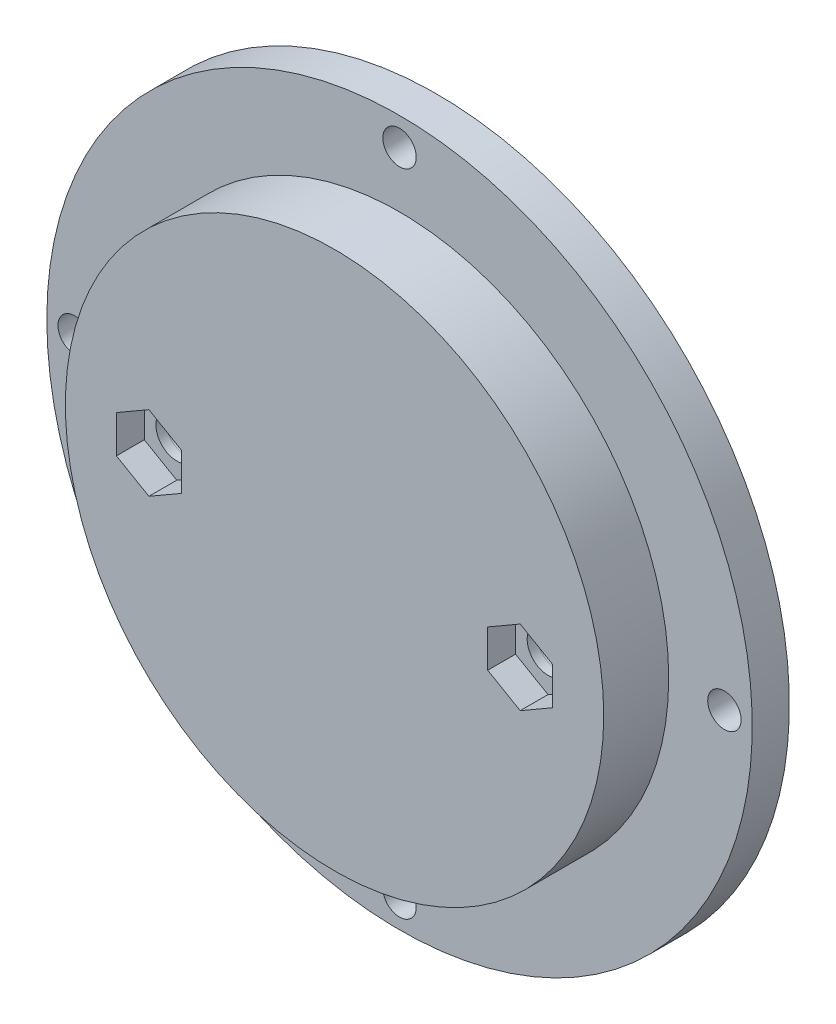
SolidWorks part; units mm, degrees
material "ｽﾃﾝﾚｽ鋼(鋳造)"
ref_plane "正面" through (0, 0, 0) normal (0, 0, 1) x (1, 0, 0)
ref_plane "平面" through (0, 0, 0) normal (0, 1, 0) x (1, 0, 0)
ref_plane "右側面" through (0, 0, 0) normal (1, 0, 0) x (0, 0, -1)
sketch "ｽｹｯﾁ1" plane through (0, 0, 0) normal (0, 1, 0) x (1, 0, 0)
  line L0 (0, 1.7) -> (0, 19.9)
  line L1 (0, 1.7) -> (0, 0) construction
  arc A0 (0, 19.9) -> (0, 1.7) centre (0, 10.8) cw
  dimension "D1" = 9.1
  dimension "D2" = 19.9
revolve "回転1" add sketch "ｽｹｯﾁ1" angle 360 about L0
sketch "ｽｹｯﾁ2" plane through (0, 0, 0) normal (0, 0, 1) x (1, 0, 0)
  line L0 (20, 0) -> (-20, 0) construction
  line L1 (-26, 0) -> (-20, 0) construction
  line L2 (-24.0086, 1.5704) -> (-9.9696, 12.6419)
  line L3 (-24.0086, -1.5704) -> (-9.9696, -12.6419)
  line L4 (0, -5.005) -> (0, 5.005) construction
  line L5 (24.0086, -1.5704) -> (9.9696, -12.6419)
  line L6 (24.0086, 1.5704) -> (9.9696, 12.6419)
  circle A0 centre (-20, 0) radius 2.25
  circle A1 centre (20, 0) radius 2.25
  arc A2 (-9.9696, -12.6419) -> (9.9696, -12.6419) centre (0, 0) ccw
  arc A3 (9.9696, 12.6419) -> (-9.9696, 12.6419) centre (0, 0) ccw
  arc A4 (24.0086, -1.5704) -> (24.0086, 1.5704) centre (22.7702, 0) ccw
  arc A5 (-24.0086, 1.5704) -> (-24.0086, -1.5704) centre (-22.7702, 0) ccw
  point P4 (0, 0)
  point P21 (26, 0)
  dimension "D2" = 4.5
  dimension "D3" = 32.2
  dimension "D4" = 2
  dimension "D1" = 40
  dimension "D5" = 26
extrude "ﾎﾞｽ - 押し出し1" add sketch "ｽｹｯﾁ2" against normal blind 1 separate body
sketch "ｽｹｯﾁ3" plane through (0, 0, -1) normal (0, 0, -1) x (-1, 0, 0)
  circle A0 centre (0, 0) radius 14.1
  arc A1 (-9.9696, -12.6419) -> (9.9696, -12.6419) centre (0, 0) ccw construction
  dimension "D1" = 2
extrude "ﾎﾞｽ - 押し出し2" add sketch "ｽｹｯﾁ3" along normal blind 14.35
fillet "ﾌｨﾚｯﾄ1" radius 4 1 edges at (-14.1, 0, -15.35)
fillet "ﾌｨﾚｯﾄ2" radius 2 1 edges at (-14.1, 0, -1)
sketch "ｽｹｯﾁ4" plane through (0, 0, 0) normal (1, 0, 0) x (0, 0, -1)
  line L0 (0, 0) -> (19.9, 0)
  arc A0 (15.35, -7.8808) -> (15.35, 7.8808) centre (10.8, 0) ccw construction
sketch "ｽｹｯﾁ5" plane through (0, 0, 0) normal (0, 0, 1) x (1, 0, 0)
  line L8 (-10.8985, 13.8197) -> (-24.9375, 2.7482)
  line L9 (-24.9375, -2.7482) -> (-10.8985, -13.8197)
  line L10 (10.8985, -13.8197) -> (24.9375, -2.7482)
  line L11 (24.9375, 2.7482) -> (10.8985, 13.8197)
  line L12 (-10.8985, 13.8197) -> (-24.9375, 2.7482)
  line L13 (-24.9375, -2.7482) -> (-10.8985, -13.8197)
  line L14 (10.8985, -13.8197) -> (24.9375, -2.7482)
  line L15 (24.9375, 2.7482) -> (10.8985, 13.8197)
  circle A4 centre (0, 0) radius 29
  arc A8 (10.8985, 13.8197) -> (-10.8985, 13.8197) centre (0, 0) ccw
  arc A9 (-24.9375, 2.7482) -> (-24.9375, -2.7482) centre (-22.7702, 0) ccw
  arc A10 (-10.8985, -13.8197) -> (10.8985, -13.8197) centre (0, 0) ccw
  arc A11 (24.9375, -2.7482) -> (24.9375, 2.7482) centre (22.7702, 0) ccw
  arc A12 (10.8985, 13.8197) -> (-10.8985, 13.8197) centre (0, 0) ccw
  arc A13 (-24.9375, 2.7482) -> (-24.9375, -2.7482) centre (-22.7702, 0) ccw
  arc A14 (-10.8985, -13.8197) -> (10.8985, -13.8197) centre (0, 0) ccw
  arc A15 (24.9375, -2.7482) -> (24.9375, 2.7482) centre (22.7702, 0) ccw
  dimension "D2" = 58
  dimension "D1" = 1.5
extrude "ﾎﾞｽ - 押し出し3" add sketch "ｽｹｯﾁ5" against normal blind 7 separate body
sketch "ｽｹｯﾁ6" plane through (0, 0, 0) normal (0, 0, 1) x (1, 0, 0)
  circle A0 centre (20, 0) radius 2.25 construction
  circle A1 centre (20, 0) radius 2.25
  circle A2 centre (-20, 0) radius 2.25 construction
  circle A3 centre (-20, 0) radius 2.25
  circle A5 centre (0, 0) radius 29
  circle A6 centre (0, 0) radius 29
  dimension "D1" = 0
extrude "ﾎﾞｽ - 押し出し4" add sketch "ｽｹｯﾁ6" along normal blind 4
sketch "ｽｹｯﾁ7" plane through (0, 0, -7) normal (0, 0, -1) x (-1, 0, 0)
  circle A0 centre (0, 0) radius 35 construction
  circle A1 centre (0, 0) radius 38
  circle A2 centre (0, 35) radius 1.8
  circle A3 centre (35, 0) radius 1.8
  circle A4 centre (0, -35) radius 1.8
  circle A5 centre (-35, 0) radius 1.8
  circle A7 centre (0, 0) radius 29
  circle A8 centre (0, 0) radius 29
  point P15 (0, 0)
  dimension "D1" = 70
  dimension "D2" = 76
  dimension "D3" = 3.6
  dimension "D5" = 0
  dimension "D4" = 4
extrude "ﾎﾞｽ - 押し出し5" add sketch "ｽｹｯﾁ7" against normal blind 4
sketch "ｽｹｯﾁ8" plane through (0, 0, 4) normal (0, 0, 1) x (1, 0, 0)
  line L1 (-20, 4.0415) -> (-23.5, 2.0207)
  line L2 (-23.5, 2.0207) -> (-23.5, -2.0207)
  line L3 (-23.5, -2.0207) -> (-20, -4.0415)
  line L4 (-20, -4.0415) -> (-16.5, -2.0207)
  line L5 (-16.5, -2.0207) -> (-16.5, 2.0207)
  line L6 (-16.5, 2.0207) -> (-20, 4.0415)
  line L7 (20, 4.0415) -> (16.5, 2.0207)
  line L8 (16.5, 2.0207) -> (16.5, -2.0207)
  line L9 (16.5, -2.0207) -> (20, -4.0415)
  line L10 (20, -4.0415) -> (23.5, -2.0207)
  line L11 (23.5, -2.0207) -> (23.5, 2.0207)
  line L12 (23.5, 2.0207) -> (20, 4.0415)
  circle A0 centre (-20, 0) radius 3.5 construction
  circle A1 centre (20, 0) radius 3.5 construction
  dimension "D1" = 7
extrude "ｶｯﾄ - 押し出し1" cut sketch "ｽｹｯﾁ8" against normal blind 3
